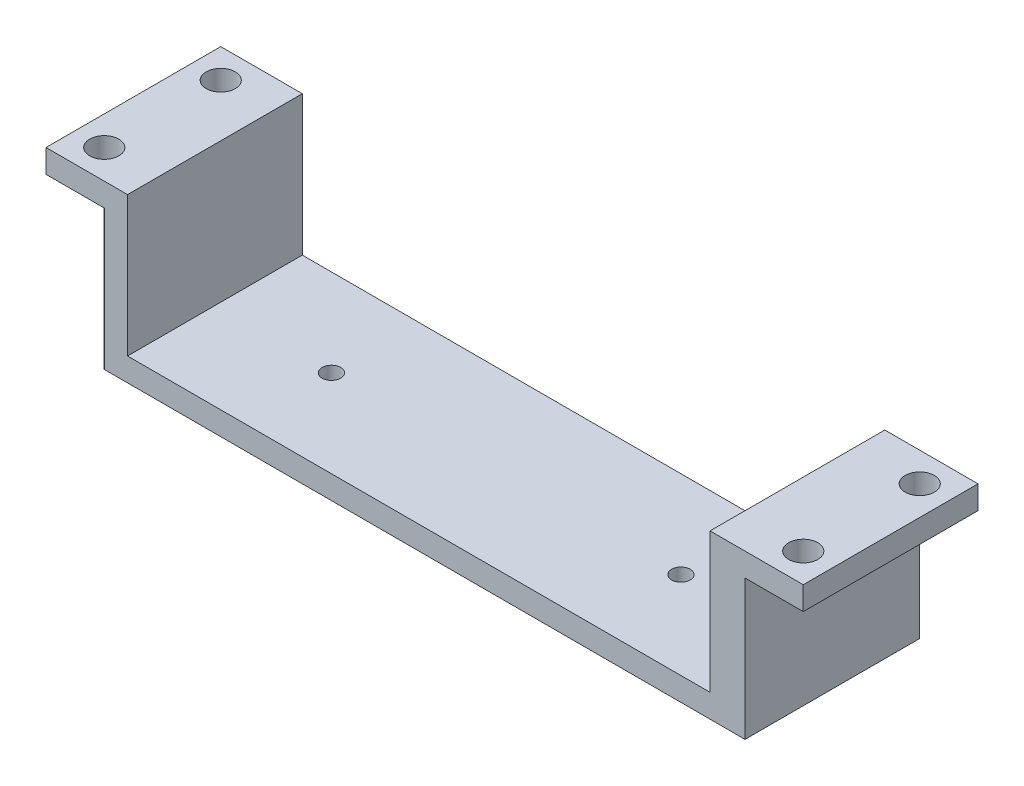
SolidWorks part; units mm, degrees
ref_plane "前视基准面" through (0, 0, 0) normal (0, 0, 1) x (1, 0, 0)
ref_plane "上视基准面" through (0, 0, 0) normal (0, 1, 0) x (1, 0, 0)
ref_plane "右视基准面" through (0, 0, 0) normal (1, 0, 0) x (0, 0, -1)
other "Configuration Table"
sketch "草图1" plane through (0, 0, 0) normal (0, 1, 0) x (1, 0, 0)
  line L0 (-4.5, 0) -> (-4.5, -2.5)
  line L69 (0, 0) -> (50, 0)
  line L70 (0, 0) -> (0, -15)
  line L71 (0, -15) -> (50, -15)
  line L72 (50, 0) -> (50, -15)
  line L73 (0, 0) -> (-2, 0)
  line L74 (0, 0) -> (0, -15)
  line L75 (0, -15) -> (-2, -15)
  line L76 (-2, 0) -> (-2, -15)
  line L77 (-2, 0) -> (-7, 0)
  line L78 (-2, 0) -> (-2, -15)
  line L79 (-2, -15) -> (-7, -15)
  line L80 (-7, 0) -> (-7, -15)
  line L81 (-4.5, -15) -> (-4.5, -12.5)
  line L82 (55.5, 0) -> (55.5, -2.5)
  line L83 (50, 0) -> (53, 0)
  line L84 (50, 0) -> (50, -15)
  line L85 (50, -15) -> (53, -15)
  line L86 (53, 0) -> (53, -15)
  line L87 (53, -15) -> (58, -15)
  line L88 (53, -15) -> (53, 0)
  line L89 (53, 0) -> (58, 0)
  line L90 (58, -15) -> (58, 0)
  line L91 (10, -7.5) -> (0, -7.5)
  line L92 (40, -7.5) -> (50, -7.5)
  circle A3 centre (-4.5, -2.5) radius 1.25
  circle A4 centre (-4.5, -12.5) radius 1.25
  circle A9 centre (55.5, -2.5) radius 1.25
  circle A13 centre (55.5, -12.5) radius 1.25
  circle A14 centre (10, -7.5) radius 0.8
  circle A15 centre (40, -7.5) radius 0.8
  dimension "D5" = 2.5
  dimension "D9" = 1.6
  dimension "D1" = 50
  dimension "D2" = 15
  dimension "D3" = 2
  dimension "D4" = 5
  dimension "D6" = 10
  dimension "D7" = 5
  dimension "D8" = 3
  dimension "D10" = 10
extrude "凸台-拉伸2" add sketch "草图1" along normal blind 2 contours L69 | L69 | L69 | L71 | L71 | L71 | A15 L72 L69 L70 A14 L74 L71 L84 region at (25, 0, 7.5)
extrude "凸台-拉伸3" add sketch "草图1<5>" along normal blind 14 contours L73 L76 L75 L70 | L86 L83 L72 L85 region at (-1, 0, 7.5) region at (51.5, 0, 7.5)
sketch "草图1<5>" plane through (0, 0, 0) normal (0, 1, 0) x (1, 0, 0) same geometry as "草图1"
extrude "凸台-拉伸4" add sketch "草图1<6>" against normal blind 2 from surface contours A4 L79 L76 L77 A3 L80 | A9 L89 L86 L87 L90 A13 region at (-4.5, 0, 7.5) region at (55.5, 0, 7.5) starting at face at (-1, 14, 7.5)
sketch "草图1<6>" plane through (0, 0, 0) normal (0, 1, 0) x (1, 0, 0) same geometry as "草图1"
